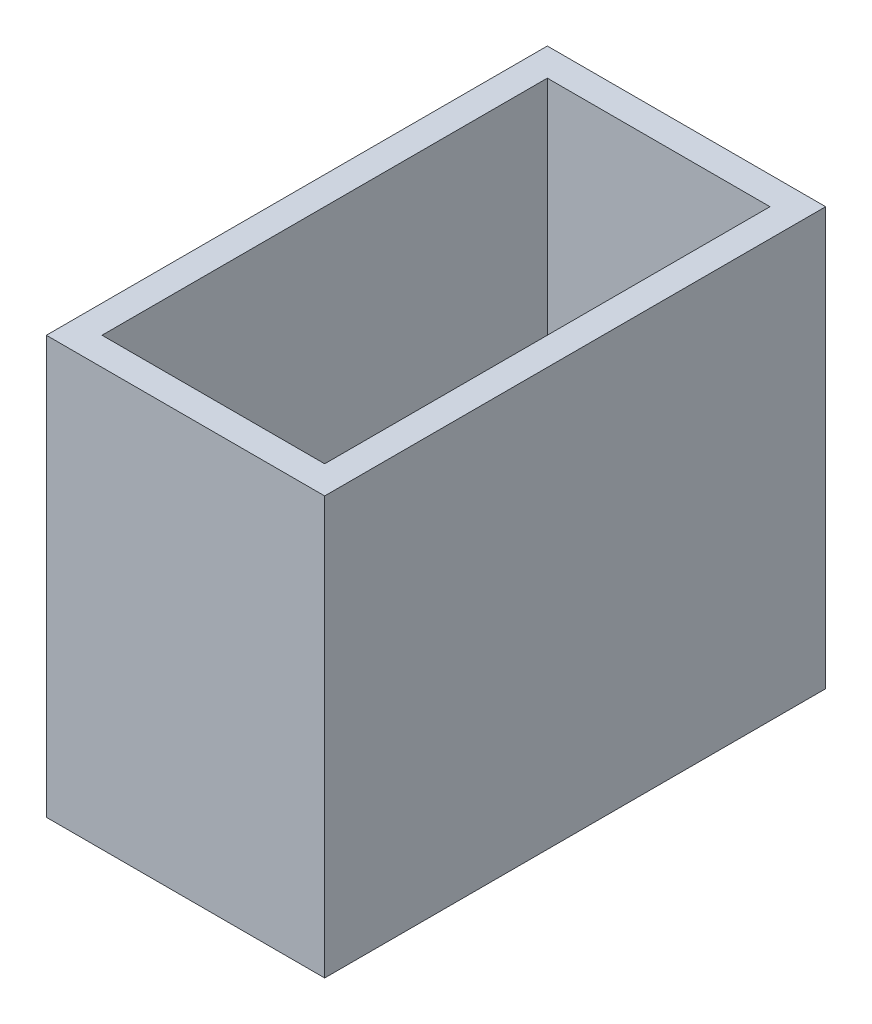
SolidWorks part; units mm, degrees
material "AISI 304"
ref_plane "前视基准面" through (0, 0, 0) normal (0, 0, 1) x (1, 0, 0)
ref_plane "上视基准面" through (0, 0, 0) normal (0, 1, 0) x (1, 0, 0)
ref_plane "右视基准面" through (0, 0, 0) normal (1, 0, 0) x (0, 0, -1)
ref_plane "InnerBottom" through (0, 0, 0) normal (0, 1, 0) x (1, 0, 0)
sketch "Circle" plane through (0, 0, 0) normal (0, 1, 0) x (1, 0, 0)
  line L0 (0, 0) -> (0, 200) construction
  dimension "R" = 200
ref_plane "InnerTop" through (0, 60, 0) normal (0, 1, 0) x (1, 0, 0)
ref_plane "SlotCenterV" through (0, 0, 0) normal (1, 0, 0) x (0, 0, -1)
ref_plane "SlotCenterH" through (0, 0, 0) normal (0, 0, 1) x (1, 0, 0)
ref_axis "CenterAxis" through (0, 0, -200) along (0, 1, 0)
sketch "STwoSlot" [suppressed] plane through (0, 0, 0) normal (0, 1, 0) x (1, 0, 0)
  line L0 (-32.1742, 0) -> (29.2905, 0) construction
  line L1 (0, 21.3687) -> (0, -19.6077) construction
  line L2 (-5, 4) -> (-5, -4)
  line L3 (-5, -4) -> (-7, -4)
  line L4 (-7, -4) -> (-7, -3)
  line L5 (-7, -3) -> (-10, -3)
  line L6 (-10, 3) -> (-7, 3)
  line L7 (-7, 3) -> (-7, 4)
  line L8 (-7, 4) -> (-5, 4)
  line L9 (5, -4) -> (7, -4)
  line L10 (7, -4) -> (7, -3)
  line L11 (7, -3) -> (10, -3)
  line L12 (10, 3) -> (7, 3)
  line L13 (7, 3) -> (7, 4)
  line L14 (7, 4) -> (5, 4)
  line L15 (5, 4) -> (5, -4)
  arc A0 (-10, -3) -> (-10, 3) centre (-10, 0) cw
  arc A1 (10, -3) -> (10, 3) centre (10, 0) ccw
  dimension "D4" = 3
  dimension "D1" = 8
  dimension "D2" = 2
  dimension "D3" = 3
  dimension "D5" = 10
sketch "STwoBase" [suppressed] plane through (0, 0, 0) normal (0, 1, 0) x (1, 0, 0)
  line L0 (0, 7.5) -> (0, -6.5) construction
  line L1 (-17.5, -7.5) -> (17.5, -7.5)
  line L2 (-17.5, -7.5) -> (-17.5, 7.5)
  line L3 (-17.5, 7.5) -> (17.5, 7.5)
  line L4 (17.5, -7.5) -> (17.5, 7.5)
  line L5 (-17.5, -7.5) -> (17.5, 7.5) construction
  line L6 (-17.5, 7.5) -> (17.5, -7.5) construction
  line L7 (-16.5, -6.5) -> (-0.5, -6.5)
  line L8 (-16.5, -6.5) -> (-16.5, 6.5)
  line L9 (-16.5, 6.5) -> (-0.5, 6.5)
  line L10 (16.5, -6.5) -> (16.5, 6.5)
  line L11 (-16.5, -6.5) -> (16.5, 6.5) construction
  line L12 (-16.5, 6.5) -> (16.5, -6.5) construction
  line L13 (-0.5, 6.5) -> (-0.5, -6.5)
  line L14 (0.5, 6.5) -> (0.5, -6.5)
  line L15 (0.5, 6.5) -> (16.5, 6.5)
  line L16 (0.5, -6.5) -> (16.5, -6.5)
  line L17 (0, 6.5) -> (0, -6.5) construction
  point P0 (0, 0)
  point P6 (0, 0)
  dimension "D1" = 35
  dimension "D5" = 1
  dimension "D2" = 15
  dimension "D3" = 1
  dimension "D4" = 1
extrude "FTwoBase" [suppressed] add sketch "STwoBase" along normal blind 15
sketch "SFiveSlotTP1" [suppressed] plane through (0, 0, 0) normal (0, 1, 0) x (1, 0, 0)
  line L0 (0, 21.9383) -> (0, -21.3523) construction
  line L1 (-37.6162, 0) -> (47.1378, 0) construction
  line L2 (-5.15, 11) -> (-5.15, 3)
  line L3 (-5.15, 3) -> (-7.55, 3)
  line L4 (-7.55, 3) -> (-7.55, 4)
  line L5 (-7.55, 4) -> (-10.55, 4)
  line L6 (-10.55, 10) -> (-7.55, 10)
  line L7 (-7.55, 10) -> (-7.55, 11)
  line L8 (-7.55, 11) -> (-5.15, 11)
  line L9 (-10.55, 7) -> (-5.15, 7) construction
  line L10 (7.55, 10) -> (7.55, 11)
  line L11 (10.55, 10) -> (7.55, 10)
  line L12 (7.55, 4) -> (10.55, 4)
  line L13 (7.55, 3) -> (7.55, 4)
  line L14 (5.15, 3) -> (7.55, 3)
  line L15 (5.15, 11) -> (5.15, 3)
  line L16 (7.55, 11) -> (5.15, 11)
  line L17 (-1.2, 7) -> (1.2, 7) construction
  line L18 (-1.2, 11.5) -> (1.2, 11.5)
  line L19 (-1.2, 11.5) -> (-1.2, 2.5)
  line L20 (-1.2, 2.5) -> (1.2, 2.5)
  line L21 (1.2, 11.5) -> (1.2, 2.5)
  line L22 (-7.2169, -4.1) -> (-2.7169, -11.8942)
  line L23 (-2.7169, -11.8942) -> (-4.7953, -13.0942)
  line L24 (-4.7953, -13.0942) -> (-9.2953, -5.3)
  line L25 (-9.2953, -5.3) -> (-7.2169, -4.1)
  line L26 (2.7169, -11.8942) -> (4.7953, -13.0942)
  line L27 (7.2169, -4.1) -> (2.7169, -11.8942)
  line L28 (4.7953, -13.0942) -> (9.2953, -5.3)
  line L29 (9.2953, -5.3) -> (7.2169, -4.1)
  line L30 (-8.2561, -4.7) -> (-3.7561, -12.4942) construction
  line L31 (-6.35, 11) -> (-6.35, 3) construction
  line L32 (6.35, 11) -> (6.35, 3) construction
  arc A0 (-10.55, 4) -> (-10.55, 10) centre (-10.55, 7) cw
  arc A1 (10.55, 4) -> (10.55, 10) centre (10.55, 7) ccw
  dimension "D4" = 3
  dimension "D1" = 8
  dimension "T3" = 2.4
  dimension "D3" = 3
  dimension "B1" = 9
  dimension "T1" = 2.4
  dimension "D7" = 7
  dimension "T2" = 2.4
  dimension "B2" = 9
  dimension "D12" = 60
  dimension "A" = 11.1
  dimension "F" = 9.5
  dimension "F2" = 12.7
sketch "SFiveBaseTP1" [suppressed] plane through (0, 0, 0) normal (0, 1, 0) x (1, 0, 0)
  line L0 (0, 29.2892) -> (0, -26.2802) construction
  line L1 (-17.5, 15) -> (17.5, 15)
  line L2 (17.5, 15) -> (17.5, 0)
  line L3 (17.5, 0) -> (7.5, -17.3205)
  line L4 (7.5, -17.3205) -> (-7.5, -17.3205)
  line L5 (-7.5, -17.3205) -> (-17.5, 0)
  line L6 (-17.5, 0) -> (-17.5, 15)
  line L8 (-16.3453, 0) -> (-6.9226, -16.3205)
  line L9 (-16.5, 14) -> (-3.75, 14)
  line L10 (-16.5, 14) -> (-16.5, 1)
  line L11 (-16.5, 1) -> (-3.75, 1)
  line L12 (16.5, 14) -> (16.5, 1)
  line L13 (-6.9226, -16.3205) -> (-0.5, -16.3205)
  line L14 (-0.5, -16.3205) -> (-0.5, 0)
  line L15 (-0.5, 0) -> (-16.3453, 0)
  line L16 (0.5, 0) -> (0.5, -16.3205)
  line L17 (0.5, -16.3205) -> (6.9226, -16.3205)
  line L18 (6.9226, -16.3205) -> (16.3453, 0)
  line L19 (16.3453, 0) -> (0.5, 0)
  line L20 (-3.75, 14) -> (-3.75, 1)
  line L21 (-2.75, 14) -> (-2.75, 1)
  line L22 (2.75, 14) -> (2.75, 1)
  line L23 (3.75, 14) -> (3.75, 1)
  line L24 (-2.75, 14) -> (2.75, 14)
  line L25 (3.75, 14) -> (16.5, 14)
  line L26 (-2.75, 1) -> (2.75, 1)
  line L27 (3.75, 1) -> (16.5, 1)
  dimension "D1" = 35
  dimension "D2" = 60
  dimension "D3" = 15
  dimension "D4" = 15
  dimension "D5" = 1
  dimension "D6" = 1
  dimension "D7" = 1
  dimension "D8" = 1
  dimension "D9" = 1
  dimension "D10" = 1
  dimension "D11" = 13
  dimension "D12" = 1
  dimension "D13" = 1
  dimension "D14" = 1
  dimension "D15" = 1
  dimension "D16" = 7.5
extrude "FFiveBaseTP1" [suppressed] add sketch "SFiveBaseTP1" along normal blind 15
sketch "SThreeSlot" [suppressed] plane through (0, 0, 0) normal (0, 1, 0) x (1, 0, 0)
  line L0 (-38.3697, 0) -> (49.7492, 0) construction
  line L1 (0, 31.5127) -> (0, -28.5949) construction
  line L2 (-9.2953, -5.3) -> (-4.7953, -13.0942)
  line L3 (-1.2, 11.5) -> (1.2, 11.5)
  line L4 (-1.2, 11.5) -> (-1.2, 2.5)
  line L5 (-1.2, 2.5) -> (1.2, 2.5)
  line L6 (1.2, 11.5) -> (1.2, 2.5)
  line L7 (-9.2953, -5.3) -> (-7.2169, -4.1)
  line L8 (-4.7953, -13.0942) -> (-2.7169, -11.8942)
  line L9 (-7.2169, -4.1) -> (-2.7169, -11.8942)
  line L10 (2.7169, -11.8942) -> (7.2169, -4.1)
  line L11 (2.7169, -11.8942) -> (4.7953, -13.0942)
  line L12 (7.2169, -4.1) -> (9.2953, -5.3)
  line L13 (4.7953, -13.0942) -> (9.2953, -5.3)
  line L14 (-1.2, 7) -> (1.2, 7) construction
  line L15 (-8.2561, -4.7) -> (-3.7561, -12.4942) construction
  dimension "B1" = 9
  dimension "T1" = 2.4
  dimension "T2" = 2.4
  dimension "B2" = 9
  dimension "F" = 9.5
  dimension "D1" = 60
  dimension "D2" = 11.1
  dimension "D3" = 7
sketch "SThreeBase" [suppressed] plane through (0, 0, 0) normal (0, 1, 0) x (1, 0, 0)
  line L0 (-19.047, 0) -> (-7.5, -20)
  line L1 (-7.5, -20) -> (7.5, -20)
  line L2 (7.5, -20) -> (19.047, 0)
  line L3 (19.047, 0) -> (5, 0)
  line L4 (5, 0) -> (5, 15)
  line L5 (5, 15) -> (-5, 15)
  line L6 (-5, 15) -> (-5, 0)
  line L7 (-19.047, 0) -> (-5, 0)
  line L8 (0, 24.0859) -> (0, -25.4306) construction
  line L9 (0, 31.5127) -> (0, -28.5949) construction
  line L11 (4, 0) -> (4, 14)
  line L12 (4, 14) -> (-4, 14)
  line L13 (-4, 14) -> (-4, 0)
  line L14 (-17.315, -1) -> (-4, -1)
  line L15 (-17.315, -1) -> (-6.9226, -19)
  line L16 (-6.9226, -19) -> (-0.5, -19)
  line L17 (6.9226, -19) -> (17.315, -1)
  line L18 (17.315, -1) -> (4, -1)
  line L19 (-4, -1) -> (-0.5, -1)
  line L20 (-4, 0) -> (4, 0)
  line L21 (-0.5, -1) -> (-0.5, -19)
  line L22 (-4, 14) -> (-4, -1) construction
  line L23 (4, -1) -> (4, 14) construction
  line L24 (0.5, -1) -> (0.5, -19)
  line L25 (0.5, -1) -> (4, -1)
  line L26 (0.5, -19) -> (6.9226, -19)
  line L28 (-6.9226, -19) -> (6.9226, -19) construction
  dimension "D3" = 15
  dimension "D6" = 1
  dimension "D7" = 1
  dimension "D2" = 15
  dimension "D1" = 10
  dimension "D4" = 20
  dimension "D5" = 60
extrude "FThreeBase" [suppressed] add sketch "SThreeBase" along normal blind 15
sketch "SUsbSlot" plane through (0, 0, 0) normal (0, 1, 0) x (1, 0, 0)
  line L0 (0, 4.2432) -> (0, -4.6578) construction
  line L2 (-2.5, -6) -> (2.5, -6)
  line L3 (-2.5, -6) -> (-2.5, 6)
  line L4 (-2.5, 6) -> (2.5, 6)
  line L5 (2.5, -6) -> (2.5, 6)
  line L6 (-2.5, -6) -> (2.5, 6) construction
  line L7 (-2.5, 6) -> (2.5, -6) construction
  point P3 (0, 0)
  dimension "UsbL" = 12
  dimension "UsbKd" = 5
sketch "SUsbBase" plane through (0, 0, 0) normal (0, 1, 0) x (1, 0, 0)
  line L1 (-5, -9) -> (5, -9)
  line L2 (-5, -9) -> (-5, 9)
  line L3 (-5, 9) -> (5, 9)
  line L4 (5, -9) -> (5, 9)
  line L5 (-5, -9) -> (5, 9) construction
  line L6 (-5, 9) -> (5, -9) construction
  line L7 (-4, 8) -> (4, 8)
  line L8 (4, -8) -> (4, 8)
  line L9 (-4, -8) -> (4, -8)
  line L10 (-4, -8) -> (-4, 8)
  dimension "D1" = 10
  dimension "D2" = 18
extrude "FUsbBase" add sketch "SUsbBase" along normal blind 15
equation "\"SlotL\"= 9"
equation "\"SlotKD\"= 2.4"
equation "\"B1@SFiveSlotTP1\"=\"SlotL\""
equation "\"B2@SFiveSlotTP1\"=\"SlotL\""
equation "\"T1@SFiveSlotTP1\"=\"SlotKD\""
equation "\"T3@SFiveSlotTP1\"=\"SlotKD\""
equation "\"T2@SFiveSlotTP1\"=\"SlotKD\""
equation "\"T1@SThreeSlot\"=\"SlotKD\""
equation "\"T2@SThreeSlot\"=\"SlotKD\""
equation "\"B1@SThreeSlot\"=\"SlotL\""
equation "\"B2@SThreeSlot\"=\"SlotL\""
equation "\"BaseTn\"=1"
equation "\"D5@SFiveBaseTP1\"=\"BaseTn\""
equation "\"D6@SFiveBaseTP1\"=\"BaseTn\""
equation "\"D7@SFiveBaseTP1\"=\"BaseTn\""
equation "\"D8@SFiveBaseTP1\"=\"BaseTn\""
equation "\"D9@SFiveBaseTP1\"=\"BaseTn\""
equation "\"D10@SFiveBaseTP1\"=\"BaseTn\""
equation "\"D12@SFiveBaseTP1\"=\"BaseTn\""
equation "\"D13@SFiveBaseTP1\"=\"BaseTn\""
equation "\"D5@STwoBase\"=\"BaseTn\""
equation "\"D3@STwoBase\"=\"BaseTn\""
equation "\"D4@STwoBase\"=\"BaseTn\""
equation "\"BaseH\"= 15"
equation "\"D1@FTwoBase\"=\"BaseH\""
equation "\"D1@FFiveBaseTP1\"=\"BaseH\""
equation "\"D6@SThreeBase\"=\"BaseTn\""
equation "\"D1@FThreeBase\"=\"BaseH\""
equation "\"D7@SThreeBase\"=\"BaseTn\""
equation "\"D3@SUsbBase\"=\"BaseTn\""
equation "\"D1@FUsbBase\"=\"BaseH\""
equation "\"D14@SFiveBaseTP1\"=\"BaseTn\""
equation "\"D15@SFiveBaseTP1\"=\"BaseTn\""
